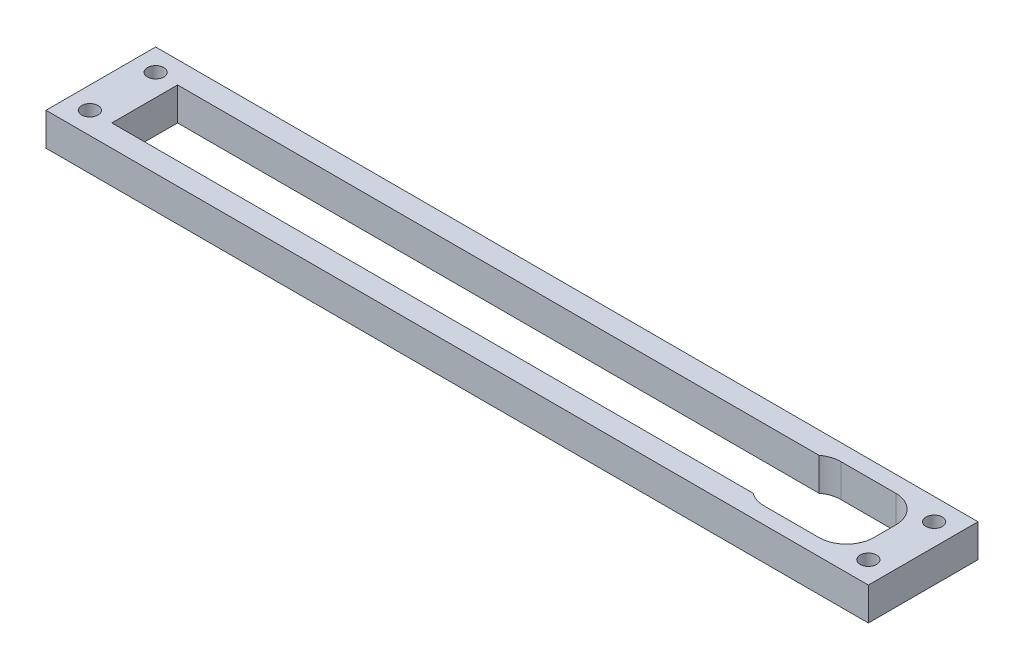
SolidWorks part; units mm, degrees
ref_plane "Front Plane" through (0, 0, 0) normal (0, 0, 1) x (1, 0, 0)
ref_plane "Top Plane" through (0, 0, 0) normal (0, 1, 0) x (1, 0, 0)
ref_plane "Right Plane" through (0, 0, 0) normal (1, 0, 0) x (0, 0, -1)
sketch "Sketch1" plane through (0, 0, 0) normal (0, 1, 0) x (1, 0, 0)
  line L0 (75, 20) -> (75, 0) construction
  line L1 (0, 0) -> (150, 0)
  line L2 (0, 0) -> (0, 20)
  line L3 (0, 20) -> (150, 20)
  line L4 (150, 0) -> (150, 20)
  line L5 (0, 10) -> (150, 10) construction
  line L6 (75, 16) -> (75, 4) construction
  line L7 (8, 16) -> (142, 16)
  line L8 (8, 16) -> (8, 4)
  line L9 (8, 4) -> (142, 4)
  line L10 (142, 16) -> (142, 4)
  line L11 (8, 10) -> (142, 10) construction
  circle A0 centre (4, 16) radius 1.5
  circle A1 centre (4, 4) radius 1.5
  circle A2 centre (146, 4) radius 1.5
  circle A3 centre (146, 16) radius 1.5
  point P17 (75, 10)
  point P18 (75, 10)
  dimension "D7" = 3
  dimension "D1" = 150
  dimension "D2" = 20
  dimension "D3" = 134
  dimension "D4" = 12
  dimension "D5" = 4
  dimension "D6" = 4
extrude "Boss-Extrude1" add sketch "Sketch1" along normal blind 6
sketch "Sketch2" plane through (0, 6, 0) normal (0, 1, 0) x (1, 0, 0)
  line L0 (92, 10) -> (-49908, 10) construction
  line L1 (142, 4) -> (142, 16) construction
  line L2 (125, 17) -> (125, 16)
  line L5 (142, 16) -> (8, 16) construction
  line L6 (134, 17) -> (134, 3) construction
  line L7 (125, 17) -> (143, 17)
  line L9 (125, 3) -> (143, 3)
  line L10 (143, 17) -> (143, 3)
  line L12 (125, 16) -> (142, 16)
  line L13 (142, 16) -> (142, 4)
  line L14 (142, 4) -> (125, 4)
  line L15 (8, 4) -> (142, 4) construction
  line L16 (125, 4) -> (125, 3)
  point P4 (142, 10)
  point P23 (134, 10)
  dimension "D1" = 1
  dimension "D2" = 18
  dimension "D3" = 14
extrude "Cut-Extrude1" cut sketch "Sketch2" against normal through all
fillet "Fillet1" radius 5 4 edges at (143, 3, -17) (143, 3, -3) (125, 3, -17) (125, 3, -3)
equation "\"TrackLength\"= 150"
equation "\"D1@Sketch1\"=\"TrackLength\""
equation "\"TrackWidth\"= \"MarbleTrackWidth\" + ( 2 * 4 )"
equation "\"D2@Sketch1\"=\"TrackWidth\""
equation "\"MarbleTrackWidth\"= \"MarbleWidth\" - 1"
equation "\"MarbleTrackLength\"= \"TrackLength\" - ( 2 * 8 )"
equation "\"D3@Sketch1\"=\"MarbleTrackLength\""
equation "\"D4@Sketch1\"=\"MarbleTrackWidth\""
equation "\"MarbleWidth\"= 13"
